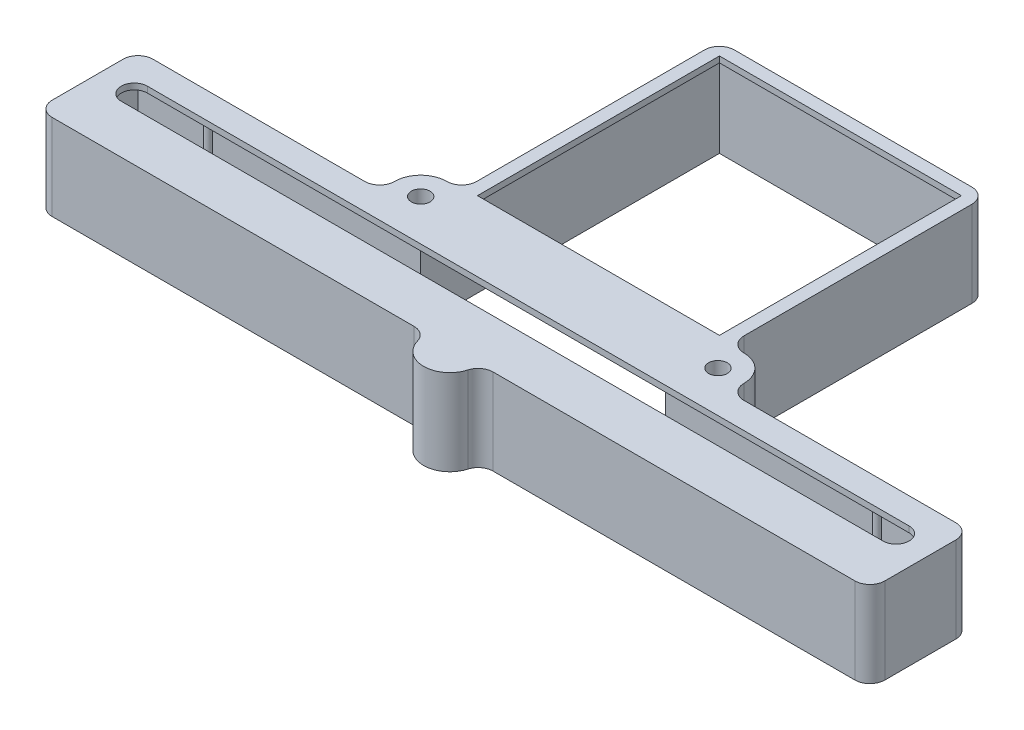
SolidWorks part; units mm, degrees
ref_plane "Front Plane" through (0, 0, 0) normal (0, 0, 1) x (1, 0, 0)
ref_plane "Top Plane" through (0, 0, 0) normal (0, 1, 0) x (1, 0, 0)
ref_plane "Right Plane" through (0, 0, 0) normal (1, 0, 0) x (0, 0, -1)
sketch "Sketch1" plane through (0, 0, 0) normal (0, 1, 0) x (1, 0, 0)
  line L0 (0, 36.3641) -> (0, -33.052) construction
  line L1 (-16.4, 25.25) -> (16.4, 25.25)
  line L2 (-16.4, 25.25) -> (-16.4, -25.25)
  line L3 (-16.4, -25.25) -> (16.4, -25.25)
  line L4 (16.4, 25.25) -> (16.4, -25.25)
  line L5 (-16.4, 25.25) -> (16.4, -25.25) construction
  line L6 (-16.4, -25.25) -> (16.4, 25.25) construction
  line L7 (-16.4, -25.25) -> (-16.4, -26.75) construction
  line L12 (-54.25, -14.75) -> (-55.75, -14.75) construction
  line L13 (-54.25, -14.75) -> (54.25, -14.75)
  line L14 (17.9, -26.75) -> (-17.9, -26.75)
  line L15 (17.9, -26.75) -> (17.9, 26.75)
  line L16 (17.9, 26.75) -> (-17.9, 26.75)
  line L17 (-17.9, -26.75) -> (-17.9, 26.75)
  line L18 (17.9, -26.75) -> (-17.9, 26.75) construction
  line L19 (17.9, 26.75) -> (-17.9, -26.75) construction
  line L20 (-16.4, 25.25) -> (-17.9, 25.25) construction
  line L21 (-16.4, 25.25) -> (-16.4, 26.75) construction
  line L22 (-54.25, -14.75) -> (-54.25, -25.25)
  line L23 (-54.25, -25.25) -> (54.25, -25.25)
  line L24 (54.25, -14.75) -> (54.25, -25.25)
  line L25 (-54.25, -14.75) -> (54.25, -25.25) construction
  line L26 (-54.25, -25.25) -> (54.25, -14.75) construction
  line L27 (-55.75, -13.25) -> (55.75, -13.25)
  line L28 (-55.75, -13.25) -> (-55.75, -26.75)
  line L29 (-55.75, -26.75) -> (55.75, -26.75)
  line L30 (55.75, -13.25) -> (55.75, -26.75)
  line L31 (-55.75, -13.25) -> (55.75, -26.75) construction
  line L32 (-55.75, -26.75) -> (55.75, -13.25) construction
  line L33 (-2, -27.25) -> (-3.5, -27.25) construction
  line L34 (-3.5, -27.25) -> (-3.5, -26.75)
  line L35 (3.5, -27.25) -> (3.5, -26.75)
  line L36 (-2, -27.25) -> (-2, -25.25)
  line L37 (2, -27.25) -> (2, -25.25)
  circle A0 centre (0, -27.25) radius 2
  circle A1 centre (0, -27.25) radius 3.5
  point P0 (0, 0)
  point P7 (0, -20)
  point P11 (0, -20)
  point P13 (0, 0)
  dimension "D6" = 4
  dimension "D1" = 32.8
  dimension "D2" = 50.5
  dimension "D3" = 1.5
  dimension "D4" = 108.5
  dimension "D5" = 10.5
extrude "Boss-Extrude1" add sketch "Sketch1" along normal blind 11.5 contours L17 L16 L15 L14 | L27 L30 L29 L28 | A1
sketch "Sketch2" plane through (0, 11.5, 0) normal (0, 1, 0) x (1, 0, 0)
  line L0 (0, 26.75) -> (0, -30.75) construction
  line L1 (17.9, 26.75) -> (-17.9, 26.75) construction
  line L3 (-16.2, 25.05) -> (-17.9, 25.05) construction
  line L4 (-16.2, -7.35) -> (16.2, -7.35)
  line L5 (-16.2, -7.35) -> (-16.2, 25.05)
  line L6 (-16.2, 25.05) -> (16.2, 25.05)
  line L7 (16.2, -7.35) -> (16.2, 25.05)
  line L8 (-16.2, -7.35) -> (16.2, 25.05) construction
  line L9 (-16.2, 25.05) -> (16.2, -7.35) construction
  line L10 (-17.9, -13.25) -> (-17.9, 26.75) construction
  line L11 (-16.2, 25.05) -> (-16.2, 26.75) construction
  arc A0 (-3.4641, -26.75) -> (3.4641, -26.75) centre (0, -27.25) ccw construction
  point P6 (0, 8.85)
  dimension "D1" = 32.4
extrude "Cut-Extrude1" cut sketch "Sketch2" against normal blind 8.7
sketch "Sketch3" plane through (0, 0, 0) normal (0, -1, 0) x (1, 0, 0)
  line L0 (-55.75, 20) -> (55.75, 20) construction
  line L1 (-55.75, 13.25) -> (-55.75, 26.75) construction
  line L2 (55.75, 13.25) -> (55.75, 26.75) construction
  line L3 (0, 30.75) -> (0, -26.75) construction
  line L4 (55.75, 26.75) -> (3.4641, 26.75) construction
  line L5 (17.9, -26.75) -> (-17.9, -26.75) construction
  line L6 (-54.25, 25.25) -> (-55.75, 25.25) construction
  line L7 (-54.25, 25.25) -> (54.25, 25.25)
  line L8 (-54.25, 25.25) -> (-54.25, 14.75)
  line L9 (-54.25, 14.75) -> (54.25, 14.75)
  line L10 (54.25, 25.25) -> (54.25, 14.75)
  line L11 (-54.25, 25.25) -> (54.25, 14.75) construction
  line L12 (-54.25, 14.75) -> (54.25, 25.25) construction
  line L13 (-54.25, 25.25) -> (-54.25, 26.75) construction
  line L14 (-2, 27.25) -> (-2, 25.25)
  line L15 (2, 27.25) -> (2, 25.25)
  arc A0 (3.4641, 26.75) -> (-3.4641, 26.75) centre (0, 27.25) ccw construction
  circle A1 centre (0, 27.25) radius 2
  point P12 (0, 20)
  dimension "D2" = 4
  dimension "D1" = 1.5
extrude "Cut-Extrude2" cut sketch "Sketch3" against normal offset from surface (10.7 mm away) 0.8 contours A1 | A1 L14 L7 | A1 L7 L15 | L10 L7 L8 L9 region at (0, 0, 20) region at (-1.5533, 0, 25.6967) region at (1.5533, 0, 25.6967) region at (0, 0, 27.25) up to face at (0, 11.5, -8.85)
sketch "Sketch4" plane through (0, 10.7, 0) normal (0, -1, 0) x (1, 0, 0)
  line L0 (-54.25, 18.5) -> (54.25, 18.5) construction
  line L1 (-54.25, 14.75) -> (-54.25, 25.25) construction
  line L2 (54.25, 25.25) -> (54.25, 14.75) construction
  line L3 (54.25, 14.75) -> (-54.25, 14.75) construction
  line L4 (51, 18.5) -> (-51, 18.5) construction
  line L5 (51, 16.75) -> (-51, 16.75)
  line L6 (51, 20.25) -> (-51, 20.25)
  arc A0 (51, 16.75) -> (51, 20.25) centre (51, 18.5) ccw
  arc A1 (-51, 20.25) -> (-51, 16.75) centre (-51, 18.5) ccw
  point P10 (0, 18.5)
  dimension "D1" = 3.75
  dimension "D2" = 3.5
  dimension "D3" = 102
extrude "Cut-Extrude3" cut sketch "Sketch4" against normal up to next
sketch "Sketch5" plane through (0, 0, 0) normal (0, -1, 0) x (1, 0, 0)
  line L0 (-17.9, -6.75) -> (17.9, -6.75) construction
  line L1 (-17.9, 13.25) -> (-17.9, -26.75) construction
  line L2 (17.9, 13.25) -> (17.9, -26.75) construction
  line L3 (-17.9, 13.25) -> (17.9, 13.25) construction
  line L4 (0, -26.75) -> (0, 13.25) construction
  line L5 (17.9, -26.75) -> (-17.9, -26.75) construction
  line L7 (-16.4, 14.75) -> (16.4, 14.75)
  line L8 (-16.4, 14.75) -> (-16.4, -25.25)
  line L9 (-16.4, -25.25) -> (16.4, -25.25)
  line L10 (16.4, 14.75) -> (16.4, -25.25)
  line L11 (-16.4, 14.75) -> (16.4, -25.25) construction
  line L12 (-16.4, -25.25) -> (16.4, 14.75) construction
  line L13 (54.25, 14.75) -> (-54.25, 14.75) construction
  line L14 (16.4, -25.25) -> (17.9, -25.25) construction
  line L15 (16.4, -25.25) -> (16.4, -26.75) construction
  point P14 (0, -5.25)
  dimension "D1" = 1.5
extrude "Cut-Extrude4" cut sketch "Sketch5" against normal up to surface (10.7 mm away) up to face at (0, 10.7, 18.5)
sketch "Sketch6" plane through (0, 10.7, 0) normal (0, -1, 0) x (1, 0, 0)
  line L0 (-16.4, -25.25) -> (-16.4, 14.75) construction
  line L1 (-16.4, 7.35) -> (16.4, 7.35)
  line L2 (-16.4, 7.35) -> (-16.4, 8.85)
  line L3 (-16.4, 8.85) -> (16.4, 8.85)
  line L4 (16.4, 7.35) -> (16.4, 8.85)
  line L5 (16.4, -25.25) -> (16.4, 14.75) construction
  line L7 (-16.2, 7.35) -> (16.2, 7.35) construction
  dimension "D1" = 1.5
extrude "Boss-Extrude2" add sketch "Sketch6" along normal offset from surface (7.7 mm away) 8.5 up to face at (0, 11.5, 18.5)
sketch "Sketch8" plane through (0, 11.5, 0) normal (0, 1, 0) x (1, 0, 0)
  line L0 (-55.75, -13.25) -> (-17.9, -13.25) construction
  line L2 (0, 31.5428) -> (0, -38.2394) construction
  line L3 (-19.9, -7.75) -> (-17.9, -7.75)
  line L4 (-17.9, -13.25) -> (-17.9, 26.75) construction
  line L5 (-23.4, -11.25) -> (-23.4, -13.25)
  line L6 (23.4, -11.25) -> (23.4, -13.25)
  line L7 (19.9, -7.75) -> (17.9, -7.75)
  line L8 (-23.4, -13.25) -> (-17.9, -13.25)
  line L9 (-17.9, -13.25) -> (-17.9, -7.75)
  line L10 (17.9, -13.25) -> (17.9, -7.75)
  line L11 (23.4, -13.25) -> (17.9, -13.25)
  circle A0 centre (-19.9, -11.25) radius 2
  circle A1 centre (19.9, -11.25) radius 2
  circle A2 centre (-19.9, -11.25) radius 3.5
  circle A3 centre (19.9, -11.25) radius 3.5
  circle A4 centre (-19.9, -11.25) radius 1.25
  circle A5 centre (19.9, -11.25) radius 1.25
  line M16 (-17.9, 26.75) -> (-17.9, -13.25)
  line M17 (-17.9, -13.25) -> (-55.75, -13.25)
  line M21 (55.75, -13.25) -> (17.9, -13.25)
  line M22 (17.9, -13.25) -> (17.9, 26.75)
  dimension "D1" = 4
  dimension "D3" = 1.5
  dimension "D2" = 2.5
extrude "Boss-Extrude5" add sketch "Sketch8" against normal up to surface (11.5 mm away) contours A2 L3 M16 | L9 A2 L8 A0 | A0 A4 | A0 L9 M17 | A2 L5 M17 | L11 A1 M22 | A1 A5 | A3 L10 A1 L11 | A3 L7 M22 | L6 A3 M21 region at (-18.8752, 11.5, 7.9848) region at (-18.3906, 11.5, 7.935) region at (-23.215, 11.5, 12.7594) region at (-18.5258, 11.5, 12.6242) region at (-18.3467, 11.5, 12.8033) region at (23.1652, 11.5, 12.2748) region at (23.215, 11.5, 12.7594) region at (18.3906, 11.5, 7.935) region at (18.3467, 11.5, 12.8033) region at (18.5258, 11.5, 12.6242) up to face at (0, 0, 13.8333)
fillet "Fillet1" radius 2 12 edges at (55.75, 5.75, 26.75) (55.75, 5.75, 13.25) (-55.75, 5.75, 26.75) (-55.75, 5.75, 13.25) (-17.9, 5.75, -26.75) (17.9, 5.75, -26.75) (-17.9, 5.75, 7.75) (-23.4, 5.75, 13.25) (23.4, 5.75, 13.25) (17.9, 5.75, 7.75) (-3.4641, 5.75, 26.75) (3.4641, 5.75, 26.75)
sketch "Sketch9" plane through (0, 10.7, 0) normal (0, -1, 0) x (1, 0, 0)
  line L0 (-35.325, 14.75) -> (-35.325, 25.25) construction
  line L1 (-54.25, 14.75) -> (-16.4, 14.75) construction
  line L2 (-2, 25.25) -> (-54.25, 25.25) construction
  line L3 (-35.325, 20) -> (-54.25, 20) construction
  line L4 (-54.25, 25.25) -> (-54.25, 14.75) construction
  line L5 (-44.7875, 20) -> (-44.7875, 14.75) construction
  line L6 (0, 41.2548) -> (0, -38.0139) construction
  circle A0 centre (-35.325, 25.25) radius 0.5
  circle A1 centre (-44.7875, 14.75) radius 0.5
  circle A2 centre (35.325, 25.25) radius 0.5
  circle A3 centre (44.7875, 14.75) radius 0.5
  dimension "D1" = 1
extrude "Boss-Extrude6" add sketch "Sketch9" along normal up to surface (10.7 mm away) up to face at (0, 0, 10.1745)
